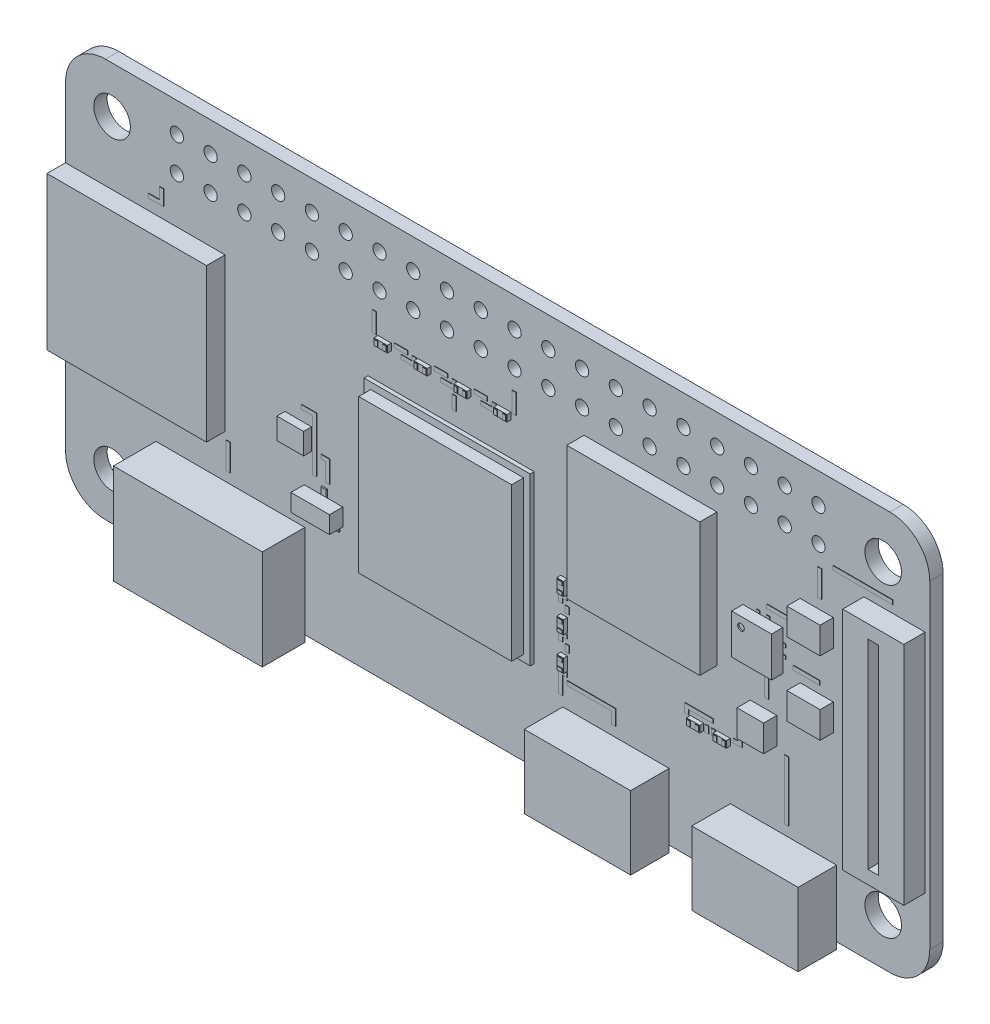
SolidWorks part; units mm, degrees
ref_plane "Front Plane" through (0, 0, 0) normal (0, 0, 1) x (1, 0, 0)
ref_plane "Top Plane" through (0, 0, 0) normal (0, 1, 0) x (1, 0, 0)
ref_plane "Right Plane" through (0, 0, 0) normal (1, 0, 0) x (0, 0, -1)
sketch "Sketch1" plane through (0, 0, 0) normal (0, 0, 1) x (1, 0, 0)
  line L0 (3, 0) -> (62, 0)
  line L1 (65, 3) -> (65, 27)
  line L2 (62, 30) -> (3, 30)
  line L3 (0, 27) -> (0, 3)
  arc A0 (62, 0) -> (65, 3) centre (62, 3) ccw
  arc A1 (65, 27) -> (62, 30) centre (62, 27) ccw
  arc A2 (3, 30) -> (0, 27) centre (3, 27) ccw
  arc A3 (0, 3) -> (3, 0) centre (3, 3) ccw
extrude "PCB" add sketch "Sketch1" along normal blind 1
ref_plane "Plane_z1" through (0, 0, 1) normal (0, 0, 1) x (1, 0, 0)
sketch "Sketch2" plane through (0, 0, 1) normal (0, 0, 1) x (1, 0, 0)
  line L0 (29.1, 20.25) -> (29.1, 21.25)
  line L1 (29.1, 21.25) -> (29.4, 21.25)
  line L2 (29.4, 21.25) -> (29.4, 20.25)
  line L3 (29.4, 20.25) -> (29.1, 20.25)
  line L4 (12.1, 7.75) -> (12.1, 9.75)
  line L5 (12.1, 9.75) -> (12.4, 9.75)
  line L6 (12.4, 9.75) -> (12.4, 7.75)
  line L7 (12.4, 7.75) -> (12.1, 7.75)
  line L8 (41.1, 5.75) -> (41.1, 6.6)
  line L9 (41.1, 6.6) -> (37.75, 6.6)
  line L10 (37.75, 6.6) -> (37.75, 6.9)
  line L11 (37.75, 6.9) -> (41.4, 6.9)
  line L12 (41.4, 6.9) -> (41.4, 5.75)
  line L13 (41.4, 5.75) -> (41.1, 5.75)
  line L14 (54.1, 5.75) -> (54.1, 10.25)
  line L15 (54.1, 10.25) -> (54.4, 10.25)
  line L16 (54.4, 10.25) -> (54.4, 5.75)
  line L17 (54.4, 5.75) -> (54.1, 5.75)
  line L18 (6.25, 22.9) -> (7.1, 22.9)
  line L19 (7.1, 22.9) -> (7.1, 23.75)
  line L20 (7.1, 23.75) -> (7.4, 23.75)
  line L21 (7.4, 23.75) -> (7.4, 22.6)
  line L22 (7.4, 22.6) -> (6.25, 22.6)
  line L23 (6.25, 22.6) -> (6.25, 22.9)
  line L24 (62.25, 24.1) -> (57.75, 24.1)
  line L25 (57.75, 24.1) -> (57.75, 24.4)
  line L26 (57.75, 24.4) -> (62.25, 24.4)
  line L27 (62.25, 24.4) -> (62.25, 24.1)
  line L28 (52.75, 19.4) -> (54.75, 19.4)
  line L29 (54.75, 19.4) -> (54.75, 19.1)
  line L30 (54.75, 19.1) -> (52.75, 19.1)
  line L31 (52.75, 19.1) -> (52.75, 19.4)
  line L32 (56.6, 21.75) -> (56.6, 23.75)
  line L33 (56.6, 23.75) -> (56.9, 23.75)
  line L34 (56.9, 23.75) -> (56.9, 21.75)
  line L35 (56.9, 21.75) -> (56.6, 21.75)
  line L36 (56.75, 16.1) -> (54.75, 16.1)
  line L37 (54.75, 16.1) -> (54.75, 16.4)
  line L38 (54.75, 16.4) -> (56.75, 16.4)
  line L39 (56.75, 16.4) -> (56.75, 16.1)
  line L40 (52.6, 13.25) -> (52.6, 14.75)
  line L41 (52.6, 14.75) -> (52.9, 14.75)
  line L42 (52.9, 14.75) -> (52.9, 13.25)
  line L43 (52.9, 13.25) -> (52.6, 13.25)
  line L44 (17.75, 14.9) -> (18.9, 14.9)
  line L45 (18.9, 14.9) -> (18.9, 10.75)
  line L46 (18.9, 10.75) -> (18.6, 10.75)
  line L47 (18.6, 10.75) -> (18.6, 14.6)
  line L48 (18.6, 14.6) -> (17.75, 14.6)
  line L49 (17.75, 14.6) -> (17.75, 14.9)
  line L50 (19.6, 10.75) -> (19.6, 12.1)
  line L51 (19.6, 12.1) -> (19.25, 12.1)
  line L52 (19.25, 12.1) -> (19.25, 12.4)
  line L53 (19.25, 12.4) -> (19.9, 12.4)
  line L54 (19.9, 12.4) -> (19.9, 10.75)
  line L55 (19.9, 10.75) -> (19.6, 10.75)
  line L56 (37.75, 7.1) -> (37.4, 7.1)
  line L57 (37.4, 7.1) -> (37.4, 5.75)
  line L58 (37.4, 5.75) -> (37.1, 5.75)
  line L59 (37.1, 5.75) -> (37.1, 7.4)
  line L60 (37.1, 7.4) -> (37.75, 7.4)
  line L61 (37.75, 7.4) -> (37.75, 7.1)
  line L62 (37.6, 8.75) -> (37.6, 9.25)
  line L63 (37.6, 9.25) -> (37.9, 9.25)
  line L64 (37.9, 9.25) -> (37.9, 8.75)
  line L65 (37.9, 8.75) -> (37.6, 8.75)
  line L66 (37.75, 9.6) -> (37.4, 9.6)
  line L67 (37.4, 9.6) -> (37.4, 9.25)
  line L68 (37.4, 9.25) -> (37.1, 9.25)
  line L69 (37.1, 9.25) -> (37.1, 9.9)
  line L70 (37.1, 9.9) -> (37.75, 9.9)
  line L71 (37.75, 9.9) -> (37.75, 9.6)
  line L72 (37.6, 11.25) -> (37.6, 11.75)
  line L73 (37.6, 11.75) -> (37.9, 11.75)
  line L74 (37.9, 11.75) -> (37.9, 11.25)
  line L75 (37.9, 11.25) -> (37.6, 11.25)
  line L76 (37.75, 12.1) -> (37.4, 12.1)
  line L77 (37.4, 12.1) -> (37.4, 11.75)
  line L78 (37.4, 11.75) -> (37.1, 11.75)
  line L79 (37.1, 11.75) -> (37.1, 12.4)
  line L80 (37.1, 12.4) -> (37.75, 12.4)
  line L81 (37.75, 12.4) -> (37.75, 12.1)
  line L82 (37.75, 13.9) -> (38.25, 13.9)
  line L83 (38.25, 13.9) -> (38.25, 13.6)
  line L84 (38.25, 13.6) -> (37.75, 13.6)
  line L85 (37.75, 13.6) -> (37.75, 13.9)
  line L86 (46.6, 9.25) -> (46.6, 9.9)
  line L87 (46.6, 9.9) -> (48.75, 9.9)
  line L88 (48.75, 9.9) -> (48.75, 9.6)
  line L89 (48.75, 9.6) -> (46.9, 9.6)
  line L90 (46.9, 9.6) -> (46.9, 9.25)
  line L91 (46.9, 9.25) -> (46.6, 9.25)
  line L92 (48.4, 9.25) -> (48.4, 8.75)
  line L93 (48.4, 8.75) -> (48.1, 8.75)
  line L94 (48.1, 8.75) -> (48.1, 9.25)
  line L95 (48.1, 9.25) -> (48.4, 9.25)
  line L96 (48.9, 9.25) -> (48.9, 8.75)
  line L97 (48.9, 8.75) -> (48.6, 8.75)
  line L98 (48.6, 8.75) -> (48.6, 9.25)
  line L99 (48.6, 9.25) -> (48.9, 9.25)
  line L100 (50.25, 9.4) -> (50.6, 9.4)
  line L101 (50.6, 9.4) -> (50.6, 10.25)
  line L102 (50.6, 10.25) -> (50.9, 10.25)
  line L103 (50.9, 10.25) -> (50.9, 9.1)
  line L104 (50.9, 9.1) -> (50.25, 9.1)
  line L105 (50.25, 9.1) -> (50.25, 9.4)
  line L106 (23.1, 22.25) -> (23.1, 23.75)
  line L107 (23.1, 23.75) -> (23.4, 23.75)
  line L108 (23.4, 23.75) -> (23.4, 22.25)
  line L109 (23.4, 22.25) -> (23.1, 22.25)
  line L110 (24.75, 22.4) -> (25.75, 22.4)
  line L111 (25.75, 22.4) -> (25.75, 22.1)
  line L112 (25.75, 22.1) -> (24.75, 22.1)
  line L113 (24.75, 22.1) -> (24.75, 22.4)
  line L114 (26.4, 22.25) -> (26.4, 21.6)
  line L115 (26.4, 21.6) -> (25.25, 21.6)
  line L116 (25.25, 21.6) -> (25.25, 21.9)
  line L117 (25.25, 21.9) -> (26.1, 21.9)
  line L118 (26.1, 21.9) -> (26.1, 22.25)
  line L119 (26.1, 22.25) -> (26.4, 22.25)
  line L120 (27.75, 22.4) -> (28.75, 22.4)
  line L121 (28.75, 22.4) -> (28.75, 22.1)
  line L122 (28.75, 22.1) -> (27.75, 22.1)
  line L123 (27.75, 22.1) -> (27.75, 22.4)
  line L124 (29.4, 22.25) -> (29.4, 21.6)
  line L125 (29.4, 21.6) -> (28.25, 21.6)
  line L126 (28.25, 21.6) -> (28.25, 21.9)
  line L127 (28.25, 21.9) -> (29.1, 21.9)
  line L128 (29.1, 21.9) -> (29.1, 22.25)
  line L129 (29.1, 22.25) -> (29.4, 22.25)
  line L130 (30.75, 22.4) -> (31.75, 22.4)
  line L131 (31.75, 22.4) -> (31.75, 22.1)
  line L132 (31.75, 22.1) -> (30.75, 22.1)
  line L133 (30.75, 22.1) -> (30.75, 22.4)
  line L134 (32.4, 22.25) -> (32.4, 21.6)
  line L135 (32.4, 21.6) -> (31.25, 21.6)
  line L136 (31.25, 21.6) -> (31.25, 21.9)
  line L137 (31.25, 21.9) -> (32.1, 21.9)
  line L138 (32.1, 21.9) -> (32.1, 22.25)
  line L139 (32.1, 22.25) -> (32.4, 22.25)
  line L140 (33.6, 22.25) -> (33.6, 23.75)
  line L141 (33.6, 23.75) -> (33.9, 23.75)
  line L142 (33.9, 23.75) -> (33.9, 22.25)
  line L143 (33.9, 22.25) -> (33.6, 22.25)
extrude "Tracks" add sketch "Sketch2" along normal blind 0.035
sketch "Sketch3" plane through (0, 0, 1) normal (0, 0, 1) x (1, 0, 0)
  line L1 (52, 15.3) -> (52.25, 15.3)
  line L2 (52, 15.3) -> (52, 15.6)
  line L3 (52, 15.6) -> (52.25, 15.6)
  line L4 (52.25, 15.3) -> (52.25, 15.6)
  line L6 (50.8, 16.5) -> (51.1, 16.5)
  line L7 (50.8, 16.5) -> (50.8, 16.75)
  line L8 (50.8, 16.75) -> (51.1, 16.75)
  line L9 (51.1, 16.5) -> (51.1, 16.75)
  line L11 (52, 18.4) -> (52.25, 18.4)
  line L12 (52, 18.4) -> (52, 18.7)
  line L13 (52, 18.7) -> (52.25, 18.7)
  line L14 (52.25, 18.4) -> (52.25, 18.7)
  line L16 (53.9, 16.5) -> (54.2, 16.5)
  line L17 (53.9, 16.5) -> (53.9, 16.75)
  line L18 (53.9, 16.75) -> (54.2, 16.75)
  line L19 (54.2, 16.5) -> (54.2, 16.75)
  line L21 (52.75, 15.3) -> (53, 15.3)
  line L22 (52.75, 15.3) -> (52.75, 15.6)
  line L23 (52.75, 15.6) -> (53, 15.6)
  line L24 (53, 15.3) -> (53, 15.6)
  line L26 (50.8, 17.25) -> (51.1, 17.25)
  line L27 (50.8, 17.25) -> (50.8, 17.5)
  line L28 (50.8, 17.5) -> (51.1, 17.5)
  line L29 (51.1, 17.25) -> (51.1, 17.5)
  line L31 (52.75, 18.4) -> (53, 18.4)
  line L32 (52.75, 18.4) -> (52.75, 18.7)
  line L33 (52.75, 18.7) -> (53, 18.7)
  line L34 (53, 18.4) -> (53, 18.7)
  line L36 (53.9, 17.25) -> (54.2, 17.25)
  line L37 (53.9, 17.25) -> (53.9, 17.5)
  line L38 (53.9, 17.5) -> (54.2, 17.5)
  line L39 (54.2, 17.25) -> (54.2, 17.5)
extrude "SMD_add00" add sketch "Sketch3" along normal blind 0.05
sketch "Sketch4" plane through (0, 0, 1) normal (0, 0, 1) x (1, 0, 0)
  line L1 (18.35, 8.05) -> (18.75, 8.05)
  line L2 (18.35, 8.05) -> (18.35, 8.75)
  line L3 (18.35, 8.75) -> (18.75, 8.75)
  line L4 (18.75, 8.05) -> (18.75, 8.75)
  line L6 (20.25, 8.05) -> (20.65, 8.05)
  line L7 (20.25, 8.05) -> (20.25, 8.75)
  line L8 (20.25, 8.75) -> (20.65, 8.75)
  line L9 (20.65, 8.05) -> (20.65, 8.75)
  line L11 (19.3, 9.65) -> (19.7, 9.65)
  line L12 (19.3, 9.65) -> (19.3, 10.35)
  line L13 (19.3, 10.35) -> (19.7, 10.35)
  line L14 (19.7, 9.65) -> (19.7, 10.35)
extrude "SMD_add01" add sketch "Sketch4" along normal blind 0.1
sketch "Sketch5" plane through (0, 0, 1) normal (0, 0, 1) x (1, 0, 0)
  line L1 (22.75, 6.75) -> (35.25, 6.75)
  line L2 (22.75, 6.75) -> (22.75, 19.25)
  line L3 (22.75, 19.25) -> (35.25, 19.25)
  line L4 (35.25, 6.75) -> (35.25, 19.25)
  line L6 (37.25, 7.5) -> (37.75, 7.5)
  line L7 (37.25, 7.5) -> (37.25, 8.5)
  line L8 (37.25, 8.5) -> (37.75, 8.5)
  line L9 (37.75, 7.5) -> (37.75, 8.5)
  line L11 (37.25, 10) -> (37.75, 10)
  line L12 (37.25, 10) -> (37.25, 11)
  line L13 (37.25, 11) -> (37.75, 11)
  line L14 (37.75, 10) -> (37.75, 11)
  line L16 (37.25, 12.5) -> (37.75, 12.5)
  line L17 (37.25, 12.5) -> (37.25, 13.5)
  line L18 (37.25, 13.5) -> (37.75, 13.5)
  line L19 (37.75, 12.5) -> (37.75, 13.5)
  line L21 (47, 8.75) -> (48, 8.75)
  line L22 (47, 8.75) -> (47, 9.25)
  line L23 (47, 9.25) -> (48, 9.25)
  line L24 (48, 8.75) -> (48, 9.25)
  line L26 (49, 8.75) -> (50, 8.75)
  line L27 (49, 8.75) -> (49, 9.25)
  line L28 (49, 9.25) -> (50, 9.25)
  line L29 (50, 8.75) -> (50, 9.25)
  line L31 (23.5, 21.75) -> (24.5, 21.75)
  line L32 (23.5, 21.75) -> (23.5, 22.25)
  line L33 (23.5, 22.25) -> (24.5, 22.25)
  line L34 (24.5, 21.75) -> (24.5, 22.25)
  line L36 (26.5, 21.75) -> (27.5, 21.75)
  line L37 (26.5, 21.75) -> (26.5, 22.25)
  line L38 (26.5, 22.25) -> (27.5, 22.25)
  line L39 (27.5, 21.75) -> (27.5, 22.25)
  line L41 (29.5, 21.75) -> (30.5, 21.75)
  line L42 (29.5, 21.75) -> (29.5, 22.25)
  line L43 (29.5, 22.25) -> (30.5, 22.25)
  line L44 (30.5, 21.75) -> (30.5, 22.25)
  line L46 (32.5, 21.75) -> (33.5, 21.75)
  line L47 (32.5, 21.75) -> (32.5, 22.25)
  line L48 (32.5, 22.25) -> (33.5, 22.25)
  line L49 (33.5, 21.75) -> (33.5, 22.25)
extrude "SMD_add02" add sketch "Sketch5" along normal blind 0.3
sketch "Sketch6" plane through (0, 0, 1) normal (0, 0, 1) x (1, 0, 0)
  line L1 (16.5, 12.2) -> (18.5, 12.2)
  line L2 (16.5, 12.2) -> (16.5, 13.8)
  line L3 (16.5, 13.8) -> (18.5, 13.8)
  line L4 (18.5, 12.2) -> (18.5, 13.8)
extrude "SMD_add03" add sketch "Sketch6" along normal blind 0.6
sketch "Sketch7" plane through (0, 0, 1) normal (0, 0, 1) x (1, 0, 0)
  line L1 (55.25, 19) -> (57.75, 19)
  line L2 (55.25, 19) -> (55.25, 21)
  line L3 (55.25, 21) -> (57.75, 21)
  line L4 (57.75, 19) -> (57.75, 21)
  line L6 (55.25, 13.5) -> (57.75, 13.5)
  line L7 (55.25, 13.5) -> (55.25, 15.5)
  line L8 (55.25, 15.5) -> (57.75, 15.5)
  line L9 (57.75, 13.5) -> (57.75, 15.5)
  line L11 (51.5, 10.5) -> (53.5, 10.5)
  line L12 (51.5, 10.5) -> (51.5, 12.5)
  line L13 (51.5, 12.5) -> (53.5, 12.5)
  line L14 (53.5, 10.5) -> (53.5, 12.5)
extrude "SMD_add04" add sketch "Sketch7" along normal blind 1
sketch "Sketch8" plane through (0, 0, 1) normal (0, 0, 1) x (1, 0, 0)
  line L1 (39, 13.5) -> (49, 13.5)
  line L2 (39, 13.5) -> (39, 23.5)
  line L3 (39, 23.5) -> (49, 23.5)
  line L4 (49, 13.5) -> (49, 23.5)
extrude "SMD_add05" add sketch "Sketch8" along normal blind 1.3
sketch "Sketch9" plane through (0, 0, 1) normal (0, 0, 1) x (1, 0, 0)
  line L1 (0, 10.25) -> (12, 10.25)
  line L2 (0, 10.25) -> (0, 21.75)
  line L3 (0, 21.75) -> (12, 21.75)
  line L4 (12, 10.25) -> (12, 21.75)
extrude "SMD_add06" add sketch "Sketch9" along normal blind 1.4
sketch "Sketch10" plane through (0, 0, 1) normal (0, 0, 1) x (1, 0, 0)
  line L1 (60.05, 6.5) -> (64.65, 6.5)
  line L2 (60.05, 6.5) -> (60.05, 23.5)
  line L3 (60.05, 23.5) -> (64.65, 23.5)
  line L4 (64.65, 6.5) -> (64.65, 23.5)
extrude "SMD_add07" add sketch "Sketch10" along normal blind 1.6
sketch "Sketch11" plane through (0, 0, 1) normal (0, 0, 1) x (1, 0, 0)
  line L1 (37.4, -0.5) -> (45.4, -0.5)
  line L2 (37.4, -0.5) -> (37.4, 5)
  line L3 (37.4, 5) -> (45.4, 5)
  line L4 (45.4, -0.5) -> (45.4, 5)
  line L6 (50, -0.5) -> (58, -0.5)
  line L7 (50, -0.5) -> (50, 5)
  line L8 (50, 5) -> (58, 5)
  line L9 (58, -0.5) -> (58, 5)
extrude "SMD_add08" add sketch "Sketch11" along normal blind 2.9
sketch "Sketch12" plane through (0, 0, 1) normal (0, 0, 1) x (1, 0, 0)
  line L1 (6.8, -0.5) -> (18, -0.5)
  line L2 (6.8, -0.5) -> (6.8, 7)
  line L3 (6.8, 7) -> (18, 7)
  line L4 (18, -0.5) -> (18, 7)
extrude "SMD_add09" add sketch "Sketch12" along normal blind 3.2
ref_plane "Plane_z1_05" through (0, 0, 1.05) normal (0, 0, 1) x (1, 0, 0)
sketch "Sketch13" plane through (0, 0, 1.05) normal (0, 0, 1) x (1, 0, 0)
  line L1 (51, 15.5) -> (54, 15.5)
  line L2 (51, 15.5) -> (51, 18.5)
  line L3 (51, 18.5) -> (54, 18.5)
  line L4 (54, 15.5) -> (54, 18.5)
extrude "SMD_add10" add sketch "Sketch13" along normal blind 0.85
ref_plane "Plane_z1_1" through (0, 0, 1.1) normal (0, 0, 1) x (1, 0, 0)
sketch "Sketch14" plane through (0, 0, 1.1) normal (0, 0, 1) x (1, 0, 0)
  line L1 (18.05, 8.55) -> (20.95, 8.55)
  line L2 (18.05, 8.55) -> (18.05, 9.85)
  line L3 (18.05, 9.85) -> (20.95, 9.85)
  line L4 (20.95, 8.55) -> (20.95, 9.85)
extrude "SMD_add11" add sketch "Sketch14" along normal blind 1
ref_plane "Plane_z1_3" through (0, 0, 1.3) normal (0, 0, 1) x (1, 0, 0)
sketch "Sketch15" plane through (0, 0, 1.3) normal (0, 0, 1) x (1, 0, 0)
  line L1 (37.3, 7.55) -> (37.7, 7.55)
  line L2 (37.3, 7.55) -> (37.3, 7.8)
  line L3 (37.3, 7.8) -> (37.7, 7.8)
  line L4 (37.7, 7.55) -> (37.7, 7.8)
  line L6 (37.3, 8.2) -> (37.7, 8.2)
  line L7 (37.3, 8.2) -> (37.3, 8.45)
  line L8 (37.3, 8.45) -> (37.7, 8.45)
  line L9 (37.7, 8.2) -> (37.7, 8.45)
  line L11 (37.3, 10.05) -> (37.7, 10.05)
  line L12 (37.3, 10.05) -> (37.3, 10.3)
  line L13 (37.3, 10.3) -> (37.7, 10.3)
  line L14 (37.7, 10.05) -> (37.7, 10.3)
  line L16 (37.3, 10.7) -> (37.7, 10.7)
  line L17 (37.3, 10.7) -> (37.3, 10.95)
  line L18 (37.3, 10.95) -> (37.7, 10.95)
  line L19 (37.7, 10.7) -> (37.7, 10.95)
  line L21 (37.3, 12.55) -> (37.7, 12.55)
  line L22 (37.3, 12.55) -> (37.3, 12.8)
  line L23 (37.3, 12.8) -> (37.7, 12.8)
  line L24 (37.7, 12.55) -> (37.7, 12.8)
  line L26 (37.3, 13.2) -> (37.7, 13.2)
  line L27 (37.3, 13.2) -> (37.3, 13.45)
  line L28 (37.3, 13.45) -> (37.7, 13.45)
  line L29 (37.7, 13.2) -> (37.7, 13.45)
  line L31 (47.05, 8.8) -> (47.3, 8.8)
  line L32 (47.05, 8.8) -> (47.05, 9.2)
  line L33 (47.05, 9.2) -> (47.3, 9.2)
  line L34 (47.3, 8.8) -> (47.3, 9.2)
  line L36 (47.7, 8.8) -> (47.95, 8.8)
  line L37 (47.7, 8.8) -> (47.7, 9.2)
  line L38 (47.7, 9.2) -> (47.95, 9.2)
  line L39 (47.95, 8.8) -> (47.95, 9.2)
  line L41 (49.05, 8.8) -> (49.3, 8.8)
  line L42 (49.05, 8.8) -> (49.05, 9.2)
  line L43 (49.05, 9.2) -> (49.3, 9.2)
  line L44 (49.3, 8.8) -> (49.3, 9.2)
  line L46 (49.7, 8.8) -> (49.95, 8.8)
  line L47 (49.7, 8.8) -> (49.7, 9.2)
  line L48 (49.7, 9.2) -> (49.95, 9.2)
  line L49 (49.95, 8.8) -> (49.95, 9.2)
  line L51 (23.55, 21.8) -> (23.8, 21.8)
  line L52 (23.55, 21.8) -> (23.55, 22.2)
  line L53 (23.55, 22.2) -> (23.8, 22.2)
  line L54 (23.8, 21.8) -> (23.8, 22.2)
  line L56 (24.2, 21.8) -> (24.45, 21.8)
  line L57 (24.2, 21.8) -> (24.2, 22.2)
  line L58 (24.2, 22.2) -> (24.45, 22.2)
  line L59 (24.45, 21.8) -> (24.45, 22.2)
  line L61 (26.55, 21.8) -> (26.8, 21.8)
  line L62 (26.55, 21.8) -> (26.55, 22.2)
  line L63 (26.55, 22.2) -> (26.8, 22.2)
  line L64 (26.8, 21.8) -> (26.8, 22.2)
  line L66 (27.2, 21.8) -> (27.45, 21.8)
  line L67 (27.2, 21.8) -> (27.2, 22.2)
  line L68 (27.2, 22.2) -> (27.45, 22.2)
  line L69 (27.45, 21.8) -> (27.45, 22.2)
  line L71 (29.55, 21.8) -> (29.8, 21.8)
  line L72 (29.55, 21.8) -> (29.55, 22.2)
  line L73 (29.55, 22.2) -> (29.8, 22.2)
  line L74 (29.8, 21.8) -> (29.8, 22.2)
  line L76 (30.2, 21.8) -> (30.45, 21.8)
  line L77 (30.2, 21.8) -> (30.2, 22.2)
  line L78 (30.2, 22.2) -> (30.45, 22.2)
  line L79 (30.45, 21.8) -> (30.45, 22.2)
  line L81 (32.55, 21.8) -> (32.8, 21.8)
  line L82 (32.55, 21.8) -> (32.55, 22.2)
  line L83 (32.55, 22.2) -> (32.8, 22.2)
  line L84 (32.8, 21.8) -> (32.8, 22.2)
  line L86 (33.2, 21.8) -> (33.45, 21.8)
  line L87 (33.2, 21.8) -> (33.2, 22.2)
  line L88 (33.2, 22.2) -> (33.45, 22.2)
  line L89 (33.45, 21.8) -> (33.45, 22.2)
extrude "SMD_add12" add sketch "Sketch15" along normal blind 0.05
sketch "Sketch16" plane through (0, 0, 1.3) normal (0, 0, 1) x (1, 0, 0)
  line L1 (23.25, 7.25) -> (34.75, 7.25)
  line L2 (23.25, 7.25) -> (23.25, 18.75)
  line L3 (23.25, 18.75) -> (34.75, 18.75)
  line L4 (34.75, 7.25) -> (34.75, 18.75)
extrude "SMD_add13" add sketch "Sketch16" along normal blind 0.9
ref_plane "Plane_y6_5" through (0, 6.5, 0) normal (0, 1, 0) x (1, 0, 0)
sketch "Sketch17" plane through (0, 6.5, 0) normal (0, 1, 0) x (1, 0, 0)
  line L1 (9.65, -1.6) -> (15.15, -1.6)
  line L2 (9.65, -1.6) -> (9.65, -3.6)
  line L3 (9.65, -3.6) -> (15.15, -3.6)
  line L4 (15.15, -1.6) -> (15.15, -3.6)
extrude "SMD_cut00" cut sketch "Sketch17" against normal blind 7
ref_plane "Plane_z1_9" through (0, 0, 1.9) normal (0, 0, 1) x (1, 0, 0)
sketch "Sketch18" plane through (0, 0, 1.9) normal (0, 0, 1) x (1, 0, 0)
  circle A0 centre (51.7, 17.8) radius 0.25
extrude "SMD_cut01" cut sketch "Sketch18" against normal blind 0.1
ref_plane "Plane_z2_6" through (0, 0, 2.6) normal (0, 0, 1) x (1, 0, 0)
sketch "Sketch19" plane through (0, 0, 2.6) normal (0, 0, 1) x (1, 0, 0)
  line L1 (61.95, 7.5) -> (62.75, 7.5)
  line L2 (61.95, 7.5) -> (61.95, 22.5)
  line L3 (61.95, 22.5) -> (62.75, 22.5)
  line L4 (62.75, 7.5) -> (62.75, 22.5)
extrude "SMD_cut02" cut sketch "Sketch19" against normal blind 1.1
sketch "Sketch20" plane through (0, 0, 1) normal (0, 0, 1) x (1, 0, 0)
  circle A0 centre (3.5, 3.5) radius 1.375
  circle A1 centre (61.5, 3.5) radius 1.375
  circle A2 centre (3.5, 26.5) radius 1.375
  circle A3 centre (61.5, 26.5) radius 1.375
  circle A4 centre (8.37, 25.23) radius 0.5
  circle A5 centre (8.37, 27.77) radius 0.5
  circle A6 centre (10.91, 25.23) radius 0.5
  circle A7 centre (10.91, 27.77) radius 0.5
  circle A8 centre (13.45, 25.23) radius 0.5
  circle A9 centre (13.45, 27.77) radius 0.5
  circle A10 centre (15.99, 25.23) radius 0.5
  circle A11 centre (15.99, 27.77) radius 0.5
  circle A12 centre (18.53, 25.23) radius 0.5
  circle A13 centre (18.53, 27.77) radius 0.5
  circle A14 centre (21.07, 25.23) radius 0.5
  circle A15 centre (21.07, 27.77) radius 0.5
  circle A16 centre (23.61, 25.23) radius 0.5
  circle A17 centre (23.61, 27.77) radius 0.5
  circle A18 centre (26.15, 25.23) radius 0.5
  circle A19 centre (26.15, 27.77) radius 0.5
  circle A20 centre (28.69, 25.23) radius 0.5
  circle A21 centre (28.69, 27.77) radius 0.5
  circle A22 centre (31.23, 25.23) radius 0.5
  circle A23 centre (31.23, 27.77) radius 0.5
  circle A24 centre (33.77, 25.23) radius 0.5
  circle A25 centre (33.77, 27.77) radius 0.5
  circle A26 centre (36.31, 25.23) radius 0.5
  circle A27 centre (36.31, 27.77) radius 0.5
  circle A28 centre (38.85, 25.23) radius 0.5
  circle A29 centre (38.85, 27.77) radius 0.5
  circle A30 centre (41.39, 25.23) radius 0.5
  circle A31 centre (41.39, 27.77) radius 0.5
  circle A32 centre (43.93, 25.23) radius 0.5
  circle A33 centre (43.93, 27.77) radius 0.5
  circle A34 centre (46.47, 25.23) radius 0.5
  circle A35 centre (46.47, 27.77) radius 0.5
  circle A36 centre (49.01, 25.23) radius 0.5
  circle A37 centre (49.01, 27.77) radius 0.5
  circle A38 centre (51.55, 25.23) radius 0.5
  circle A39 centre (51.55, 27.77) radius 0.5
  circle A40 centre (54.09, 25.23) radius 0.5
  circle A41 centre (54.09, 27.77) radius 0.5
  circle A42 centre (56.63, 25.23) radius 0.5
  circle A43 centre (56.63, 27.77) radius 0.5
extrude "Holes" cut sketch "Sketch20" against normal blind 1
equation "\"pcb_t\" = 1.0mm"
equation "\"D1@PCB\" = \"pcb_t\""
